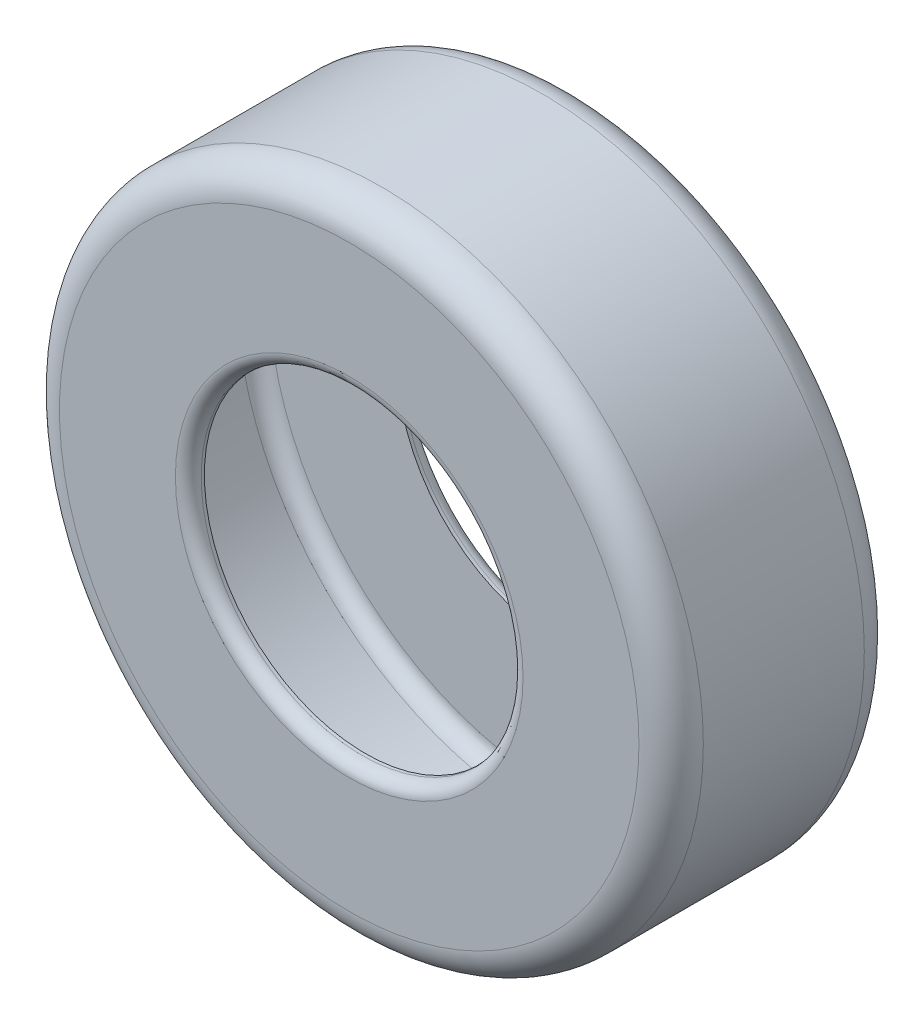
SolidWorks part; units mm, degrees
ref_plane "Front Plane" through (0, 0, 0) normal (0, 0, 1) x (1, 0, 0)
ref_plane "Top Plane" through (0, 0, 0) normal (0, 1, 0) x (1, 0, 0)
ref_plane "Right Plane" through (0, 0, 0) normal (1, 0, 0) x (0, 0, -1)
sketch "Sketch3" plane through (0, 0, 0) normal (0, 0, 1) x (1, 0, 0)
  line L0 (12.7, 0) -> (12.6807, 0.6996)
  circle A0 centre (0, 0) radius 12.7
  dimension "D1" = 12.6952
extrude "Extrude-Thin1" add sketch "Sketch3" along normal blind 17.78 thin contours A0 thin type one direction wall 12.7
fillet "Fillet1" radius 2.54 2 edges at (25.4, 0, 0) (25.4, 0, 17.78)
fillet "Fillet2" radius 1.016 2 edges at (12.7, 0, 0) (12.7, 0, 17.78)
shell "Shell1" thickness 1.27 removed face at (12.7, 0, 1.016)
